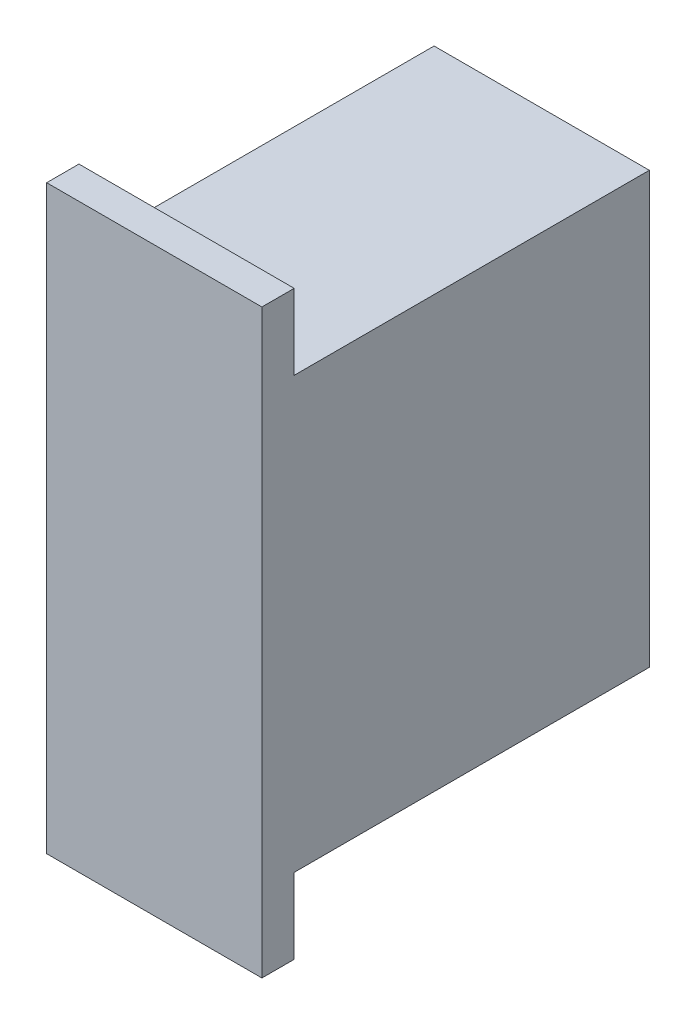
SolidWorks part; units mm, degrees
ref_plane "Front Plane" through (0, 0, 0) normal (0, 0, 1) x (1, 0, 0)
ref_plane "Top Plane" through (0, 0, 0) normal (0, 1, 0) x (1, 0, 0)
ref_plane "Right Plane" through (0, 0, 0) normal (1, 0, 0) x (0, 0, -1)
sketch "Sketch1" plane through (0, 0, 0) normal (0, 0, 1) x (1, 0, 0)
  line L1 (-10, -20) -> (10, -20)
  line L2 (-10, -20) -> (-10, 20)
  line L3 (-10, 20) -> (10, 20)
  line L4 (10, -20) -> (10, 20)
  line L5 (-10, -20) -> (10, 20) construction
  line L6 (-10, 20) -> (10, -20) construction
  point P0 (0, 0)
  dimension "D1" = 20
  dimension "D2" = 40
extrude "Boss-Extrude1" add sketch "Sketch1" along normal blind 36
sketch "Sketch2" plane through (0, 0, 36) normal (0, 0, 1) x (1, 0, 0)
  line L0 (11, 0) -> (-11, 0) construction
  line L1 (-10, 20) -> (10, 20)
  line L2 (-10, 20) -> (-10, 27)
  line L3 (-10, 27) -> (10, 27)
  line L4 (10, 20) -> (10, 27)
  line L5 (-10, -27) -> (10, -27)
  line L6 (10, -20) -> (10, -27)
  line L7 (-10, -20) -> (10, -20)
  line L8 (-10, -20) -> (-10, -27)
  point P5 (10, 20)
  dimension "D1" = 7
  dimension "D2" = 20
extrude "Boss-Extrude5" add sketch "Sketch2" against normal blind 3
